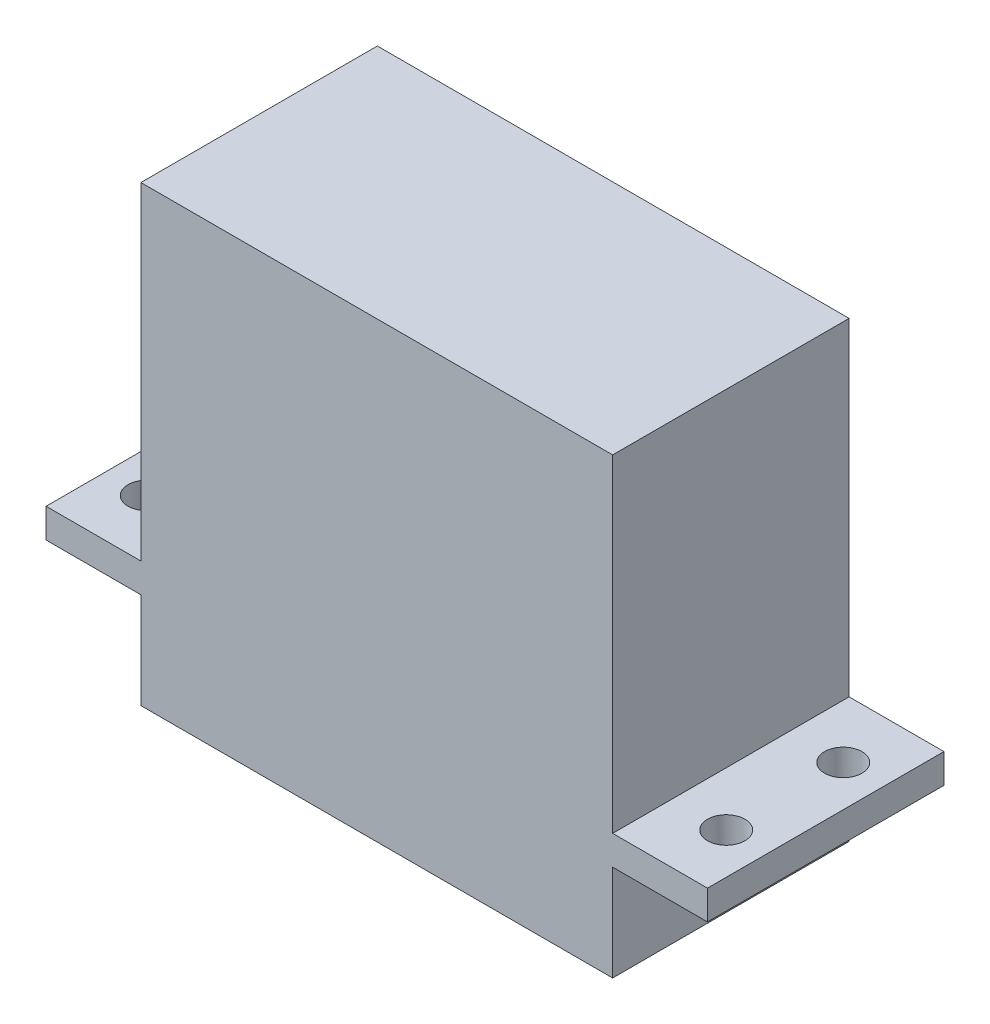
SolidWorks part; units mm, degrees
ref_plane "Front Plane" through (0, 0, 0) normal (0, 0, 1) x (1, 0, 0)
ref_plane "Top Plane" through (0, 0, 0) normal (0, 1, 0) x (1, 0, 0)
ref_plane "Right Plane" through (0, 0, 0) normal (1, 0, 0) x (0, 0, -1)
sketch "Case Sketch" plane through (0, 0, 0) normal (0, 0, 1) x (1, 0, 0)
  line L0 (-10.05, 4) -> (30.25, 4)
  line L1 (30.25, 4) -> (30.25, 42.7)
  line L2 (30.25, 42.7) -> (-10.05, 42.7)
  line L3 (-10.05, 42.7) -> (-10.05, 4)
extrude "Case" add sketch "Case Sketch" along normal mid plane 20.2
ref_axis "Stem Axis" through (0, -2.135, 0) along (0, 1, 0)
sketch "Tabs Sketch" plane through (0, 0, 0) normal (0, 0, 1) x (1, 0, 0)
  line L0 (-18.15, 12.2) -> (-10.05, 12.2)
  line L1 (-10.05, 12.2) -> (-10.05, 14.7)
  line L2 (-10.05, 14.7) -> (-18.15, 14.7)
  line L3 (-18.15, 14.7) -> (-18.15, 12.2)
  line L4 (30.25, 12.2) -> (38.35, 12.2)
  line L5 (38.35, 12.2) -> (38.35, 14.7)
  line L6 (38.35, 14.7) -> (30.25, 14.7)
  line L7 (30.25, 14.7) -> (30.25, 12.2)
extrude "Tabs" add sketch "Tabs Sketch" along normal mid plane 20.2
sketch "Shaft Sketch" plane through (0, 0, 0) normal (0, 0, 1) x (1, 0, 0)
  line L0 (0, -500) -> (0, 500) construction
  line L1 (0, 0) -> (3, 0)
  line L2 (3, 0) -> (3, 4)
  line L3 (3, 4) -> (0, 4)
  line L4 (0, 4) -> (0, 0)
revolve "Shaft" add sketch "Shaft Sketch" angle 360 about L0
sketch "Tab Holes Sketch" plane through (0, 0, 0) normal (0, 1, 0) x (1, 0, 0)
  circle A0 centre (-14.65, -5) radius 1.6
  circle A1 centre (-14.65, 5) radius 1.6
  circle A2 centre (34.85, -5) radius 1.6
  circle A3 centre (34.85, 5) radius 1.6
extrude "Tab Holes" cut sketch "Tab Holes Sketch" against normal mid plane 105.4
